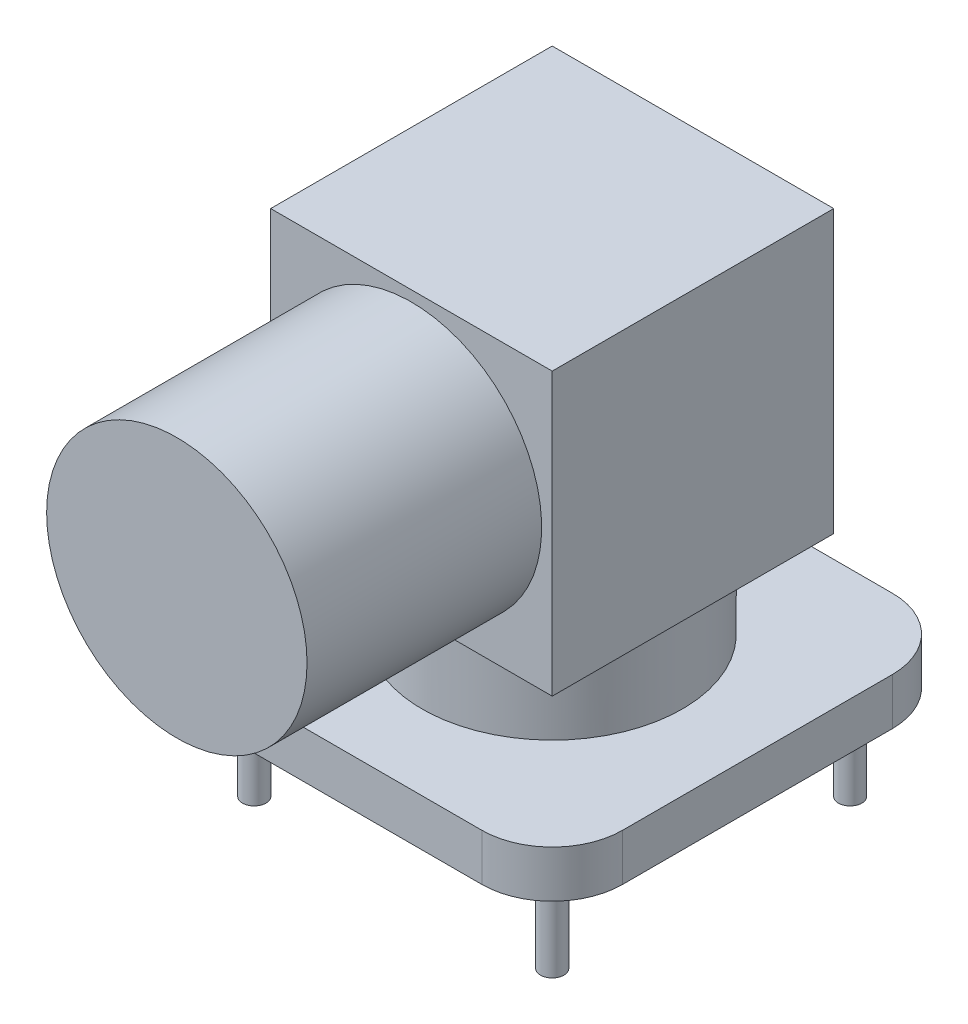
SolidWorks part; units mm, degrees
ref_plane "Ebene vorne" through (0, 0, 0) normal (0, 0, 1) x (1, 0, 0)
ref_plane "Ebene oben" through (0, 0, 0) normal (0, 1, 0) x (1, 0, 0)
ref_plane "Ebene rechts" through (0, 0, 0) normal (1, 0, 0) x (0, 0, -1)
sketch "Skizze1" plane through (0, 0, 0) normal (0, 1, 0) x (1, 0, 0)
  line L1 (-5.75, -8.75) -> (5.75, -8.75)
  line L2 (-8.75, -5.75) -> (-8.75, 5.75)
  line L3 (-5.75, 8.75) -> (5.75, 8.75)
  line L4 (8.75, -5.75) -> (8.75, 5.75)
  line L5 (-8.75, -8.75) -> (8.75, 8.75) construction
  line L6 (-8.75, 8.75) -> (8.75, -8.75) construction
  arc A0 (-5.75, -8.75) -> (-8.75, -5.75) centre (-5.75, -5.75) cw
  arc A1 (5.75, -8.75) -> (8.75, -5.75) centre (5.75, -5.75) ccw
  arc A2 (5.75, 8.75) -> (8.75, 5.75) centre (5.75, 5.75) cw
  arc A3 (-8.75, 5.75) -> (-5.75, 8.75) centre (-5.75, 5.75) cw
  point P0 (0, 0)
  dimension "D3" = 3
  dimension "D1" = 17.5
  dimension "D2" = 17.5
extrude "Aufsatz-Linear austragen1" add sketch "Skizze1" along normal blind 2
sketch "Skizze2" plane through (0, 0, 0) normal (0, -1, 0) x (1, 0, 0)
  line L1 (-6.35, 6.35) -> (6.35, 6.35) construction
  line L2 (-6.35, 6.35) -> (-6.35, -6.35) construction
  line L3 (-6.35, -6.35) -> (6.35, -6.35) construction
  line L4 (6.35, 6.35) -> (6.35, -6.35) construction
  line L5 (-6.35, 6.35) -> (6.35, -6.35) construction
  line L6 (-6.35, -6.35) -> (6.35, 6.35) construction
  circle A0 centre (6.35, -6.35) radius 0.5
  circle A1 centre (-6.35, 6.35) radius 0.5
  circle A2 centre (6.35, 6.35) radius 0.5
  circle A3 centre (-6.35, -6.35) radius 0.5
  circle A4 centre (0, 0) radius 0.5
  point P0 (0, 0)
  dimension "D2" = 1
  dimension "D1" = 12.7
extrude "Aufsatz-Linear austragen2" add sketch "Skizze2" along normal blind 4
sketch "Skizze3" plane through (0, 2, 0) normal (0, 1, 0) x (1, 0, 0)
  circle A0 centre (0, 0) radius 5.55
  dimension "D1" = 11.1
extrude "Aufsatz-Linear austragen3" add sketch "Skizze3" along normal blind 3.7
sketch "Skizze4" plane through (0, 5.7, 0) normal (0, 1, 0) x (1, 0, 0)
  line L1 (-6, 6) -> (6, 6)
  line L2 (-6, 6) -> (-6, -6)
  line L3 (-6, -6) -> (6, -6)
  line L4 (6, 6) -> (6, -6)
  line L5 (-6, 6) -> (6, -6) construction
  line L6 (-6, -6) -> (6, 6) construction
  point P0 (0, 0)
  dimension "D1" = 12
extrude "Aufsatz-Linear austragen4" add sketch "Skizze4" along normal blind 12
sketch "Skizze5" plane through (0, 0, 6) normal (0, 0, 1) x (1, 0, 0)
  line L0 (-6, 17.7) -> (6, 5.7) construction
  line L3 (6, 17.7) -> (-6, 5.7) construction
  circle A0 centre (0, 11.7) radius 5.55
  point P9 (0, 11.7)
  dimension "D1" = 11.1
extrude "Aufsatz-Linear austragen5" add sketch "Skizze5" along normal blind 10
